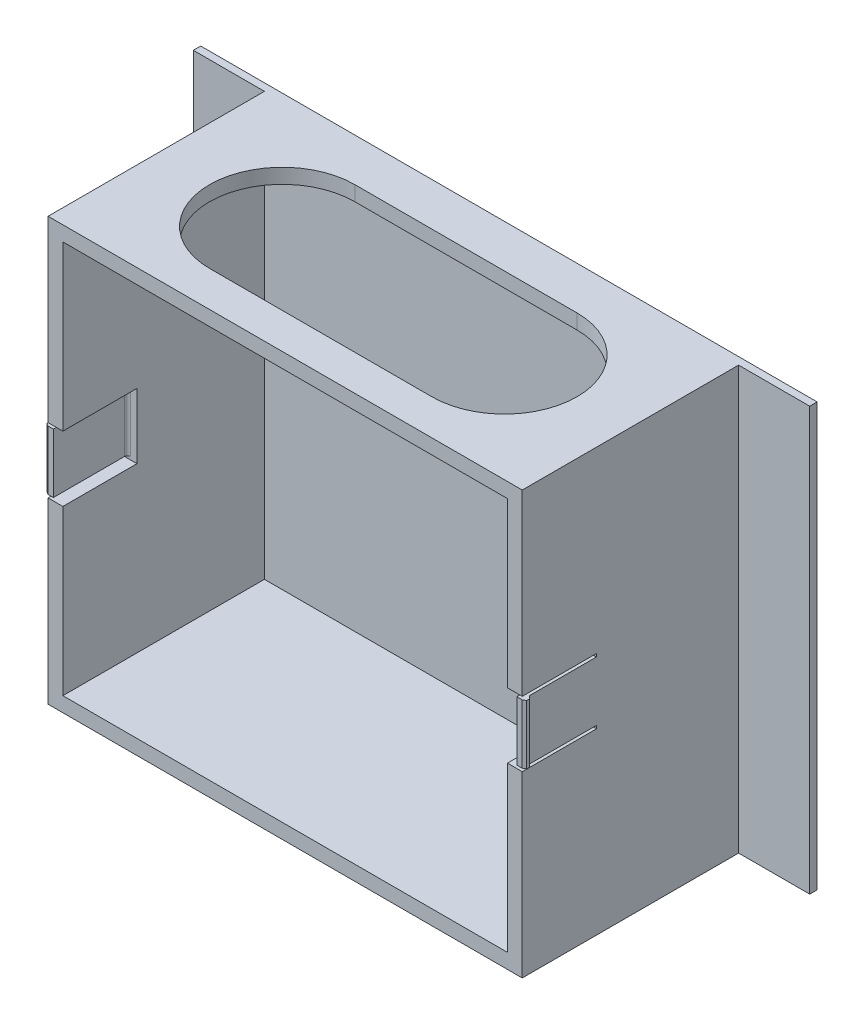
SolidWorks part; units mm, degrees
ref_plane "Front Plane" through (0, 0, 0) normal (0, 0, 1) x (1, 0, 0)
ref_plane "Top Plane" through (0, 0, 0) normal (0, 1, 0) x (1, 0, 0)
ref_plane "Right Plane" through (0, 0, 0) normal (1, 0, 0) x (0, 0, -1)
sketch "Sketch2" plane through (0, 0, 0) normal (0, 1, 0) x (1, 0, 0)
  line L1 (-101.6, -46.355) -> (101.6, -46.355)
  line L2 (-101.6, -46.355) -> (-101.6, 46.355)
  line L3 (-101.6, 46.355) -> (101.6, 46.355)
  line L4 (101.6, -46.355) -> (101.6, 46.355)
  line L5 (-101.6, -46.355) -> (101.6, 46.355) construction
  line L6 (-101.6, 46.355) -> (101.6, -46.355) construction
  point P0 (0, 0)
  dimension "D1" = 203.2
  dimension "D2" = 92.71
extrude "Boss-Extrude1" add sketch "Sketch2" along normal blind 181.102
sketch "Sketch3" plane through (0, 0, 46.355) normal (0, 0, 1) x (1, 0, 0)
  line L0 (-95.25, 6.35) -> (95.25, 6.35)
  line L1 (95.25, 6.35) -> (95.25, 174.752)
  line L2 (95.25, 174.752) -> (-95.25, 174.752)
  line L3 (-95.25, 174.752) -> (-95.25, 6.35)
  line L4 (-101.6, 0) -> (101.6, 0)
  line L5 (101.6, 0) -> (101.6, 181.102)
  line L6 (101.6, 181.102) -> (-101.6, 181.102)
  line L7 (-101.6, 181.102) -> (-101.6, 0)
  line L8 (-101.6, 0) -> (101.6, 0) construction
  line L9 (101.6, 0) -> (101.6, 181.102) construction
  line L10 (101.6, 181.102) -> (-101.6, 181.102) construction
  line L11 (-101.6, 181.102) -> (-101.6, 0) construction
  dimension "D1" = 0
  dimension "D2" = 6.35
extrude "Cut-Extrude1" cut sketch "Sketch3" against normal blind 86.36 contours L3 L0 L1 L2
sketch "Sketch5" plane through (0, 181.102, 0) normal (0, -1, 0) x (1, 0, 0)
  line L0 (-47.625, 0) -> (47.625, 0) construction
  line L1 (-47.625, 31.115) -> (47.625, 31.115)
  line L2 (-47.625, -31.115) -> (47.625, -31.115)
  arc A0 (-47.625, 31.115) -> (-47.625, -31.115) centre (-47.625, 0) ccw
  arc A1 (47.625, -31.115) -> (47.625, 31.115) centre (47.625, 0) ccw
  point P2 (0, 0)
  dimension "D1" = 31.115
  dimension "D2" = 95.25
extrude "Cut-Extrude2" cut sketch "Sketch5" along normal up to next contours A1 L1 A0 L2
sketch "Sketch6" plane through (0, 0, -46.355) normal (0, 0, -1) x (-1, 0, 0)
  line L0 (-101.6, 181.102) -> (-101.6, 0) construction
  line L1 (-132.08, 181.102) -> (132.08, 181.102)
  line L2 (-132.08, 181.102) -> (-132.08, 0)
  line L3 (-132.08, 0) -> (132.08, 0)
  line L4 (132.08, 181.102) -> (132.08, 0)
  line L5 (101.6, 181.102) -> (101.6, 0) construction
  dimension "D1" = 30.48
  dimension "D2" = 30.48
extrude "Boss-Extrude2" add sketch "Sketch6" along normal blind 3.175
sketch "Sketch8" plane through (0, 0, 46.355) normal (0, 0, 1) x (1, 0, 0)
  line L0 (-101.6, 181.102) -> (-101.6, 0) construction
  line L1 (-99.314, 103.251) -> (-95.25, 103.251)
  line L2 (-99.314, 103.251) -> (-99.314, 77.851)
  line L3 (-99.314, 77.851) -> (-95.25, 77.851)
  line L4 (-95.25, 103.251) -> (-95.25, 77.851)
  line L6 (-101.6, 181.102) -> (101.6, 181.102) construction
  line L8 (-101.6, 181.102) -> (-101.6, 0) construction
  line L9 (-95.25, 103.251) -> (-101.6, 103.251)
  line L10 (-95.25, 103.251) -> (-95.25, 104.521)
  line L11 (-95.25, 104.521) -> (-101.6, 104.521)
  line L12 (-101.6, 103.251) -> (-101.6, 104.521)
  line L14 (-95.25, 77.851) -> (-101.6, 77.851)
  line L15 (-95.25, 77.851) -> (-95.25, 76.581)
  line L16 (-95.25, 76.581) -> (-101.6, 76.581)
  line L17 (-101.6, 77.851) -> (-101.6, 76.581)
  line M3 (-95.25, 6.35) -> (-95.25, 174.752)
  line M10 (-101.6, 181.102) -> (-101.6, 0)
  dimension "D1" = 2.286
  dimension "D2" = 4.064
  dimension "D3" = 25.4
  dimension "D4" = 77.851
  dimension "D5" = 1.27
  dimension "D6" = 1.27
extrude "Cut-Extrude3" cut sketch "Sketch8" against normal blind 31.75 contours L2 L3 L1 M3 | L16 L3 L14 M3 M10 | L10 L11 L12 L9 region at (-97.282, 90.551, 46.355) region at (-98.425, 77.216, 46.355)
fillet "Fillet1" radius 1.27 1 edges at (-99.314, 90.551, 14.605)
ref_plane "Plane1" through (0, 90.551, 0) normal (0, -1, 0) x (-1, 0, 0)
sketch "Sketch10" plane through (0, 90.551, 0) normal (0, -1, 0) x (-1, 0, 0)
  line L0 (101.6, -46.355) -> (102.8077, -45.6577)
  line L1 (101.6, 46.355) -> (101.6, -46.355) construction
  line L2 (102.8077, -45.6577) -> (102.8077, -44.3877)
  line L3 (102.8077, -44.3877) -> (101.6, -43.18)
  line L4 (102.8077, -45.0227) -> (102.3823, -45.0227) construction
  line L5 (101.6, -46.355) -> (101.6, -43.18)
  dimension "D1" = 30
  dimension "D2" = 45
  dimension "D3" = 1.27
  dimension "D4" = 3.175
extrude "Boss-Extrude3" add sketch "Sketch10" along normal blind 12.7 and the other way blind 12.7 contours L0 L2 L3 L5
ref_plane "Plane2" through (0, 0, 0) normal (1, 0, 0) x (0, 0, -1)
mirror "Mirror1" about plane through (0, 0, 0) normal (1, 0, 0) of "Boss-Extrude3", "Fillet1", "Cut-Extrude3"
